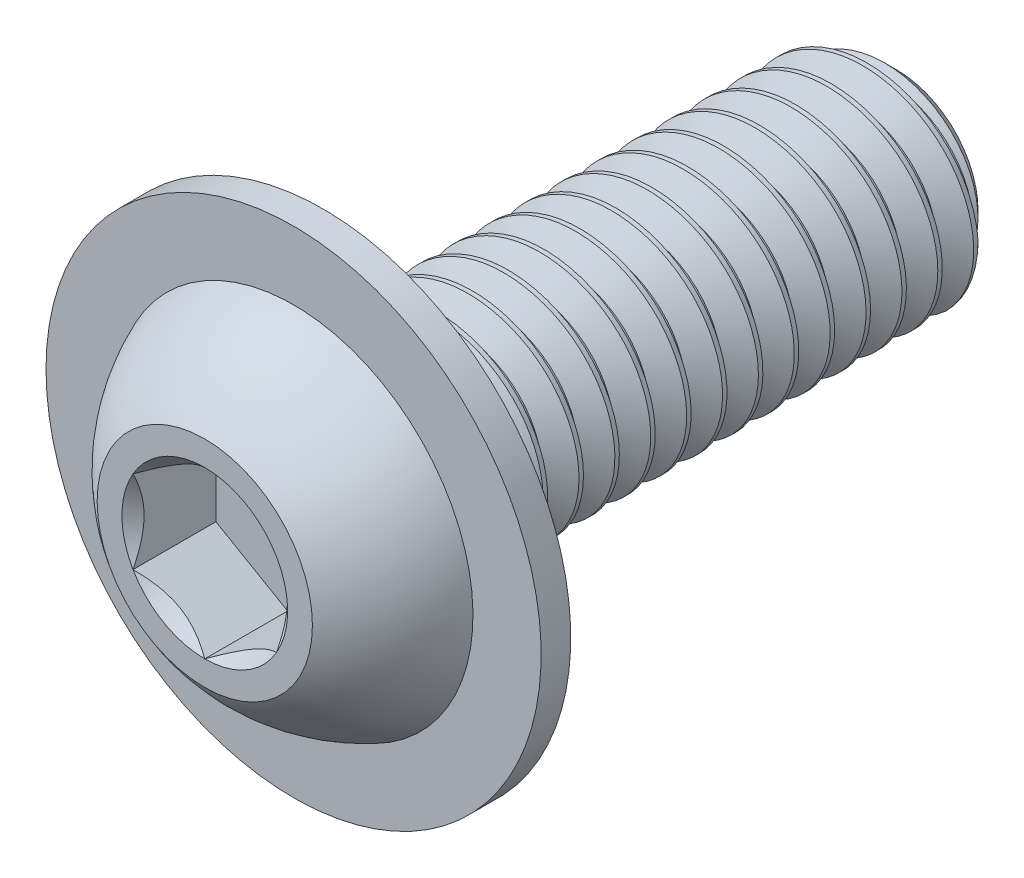
SolidWorks part; units mm, degrees
ref_plane "Front" through (0, 0, 0) normal (0, 0, 1) x (1, 0, 0)
ref_plane "Top" through (0, 0, 0) normal (0, 1, 0) x (1, 0, 0)
ref_plane "Right" through (0, 0, 0) normal (1, 0, 0) x (0, 0, -1)
sketch "Sketch1" plane through (0, 0, 0) normal (1, 0, 0) x (0, 0, -1)
  line L2 (1.65, 1.5) -> (9.65, 1.5)
  line L3 (9.65, 1.5) -> (9.65, 0)
  line L4 (9.65, 0) -> (1.65, 0)
  line L6 (1.2375, 2.5) -> (1.65, 2.5) construction
  line L7 (9.65, 1.5) -> (9.65, -1.5) construction
  line L8 (0, 0) -> (1.65, 0) construction
  line L9 (1.65, 2.5) -> (1.65, -2.5) construction
  line L11 (1.65, 1.5) -> (1.65, 0)
  line L13 (0, 1) -> (0, -1) construction
  line L14 (0, 1) -> (0, 1.5) construction
  line L15 (1.2375, 2.5) -> (1.2375, 3.45) construction
  line L16 (1.2375, 3.45) -> (1.65, 3.45) construction
  line L17 (1.65, 3.45) -> (1.65, 2.5) construction
  line L18 (1.65, 3.45) -> (1.65, -3.45) construction
  arc A3 (0, 1.5) -> (1.2375, 2.5) centre (2.2349, 0) cw construction
  dimension "D1" = 0.4125
revolve "Revolve1" add sketch "Sketch1" angle 360 mid plane about L4
sketch "Sketch3" plane through (0, 0, -9.65) normal (0, 0, -1) x (-1, 0, 0)
  circle A0 centre (0, 0) radius 1.5
curve "Helix/Spiral1" pitch 0.5 height 8.5 radius 1.5 centre (0, 0, -9.65) axis (0, 0, 1) start towards (0, 1, 0)
sketch "Sketch2" plane through (0, 0, 0) normal (1, 0, 0) x (0, 0, -1)
  line L0 (9.65, 1.5) -> (10.0875, 1.5)
  line L1 (10.0875, 1.5) -> (9.9, 1.1752)
  line L2 (9.9, 1.1752) -> (9.8375, 1.1752)
  line L3 (9.8375, 1.1752) -> (9.65, 1.5)
  line L4 (9.7438, 1.3376) -> (9.9938, 1.3376) construction
  dimension "D1" = 60
  dimension "D2" = 0.0625
  dimension "D3" = 0.25
chamfer "Chamfer1" distance 0.375 angle 45 1 edges at (0, 1.5, -9.65)
sweep "Cut-Sweep1" cut profiles "Sketch2" path "Helix/Spiral1" align with end faces yes
sketch "Sketch7" plane through (0, 0, 0) normal (1, 0, 0) x (0, 0, -1)
  line L6 (1.2375, 2.5) -> (1.65, 2.5) construction
  line L8 (0, 0) -> (1.65, 0) construction
  line L11 (1.65, 2.5) -> (1.65, -2.5) construction
  line L12 (1.2375, 2.5) -> (1.65, 2.5)
  line L13 (0, 0) -> (1.65, 0)
  line L14 (0, 1) -> (0, -1) construction
  line L15 (1.65, 2.5) -> (1.65, 0)
  line L16 (0, 1.5) -> (0, 0)
  arc A2 (1.2375, 2.5) -> (0, 1.5) centre (2.2349, 0) ccw construction
  arc A3 (1.2375, 2.5) -> (0, 1.5) centre (2.2349, 0) ccw
revolve "Revolve2" add sketch "Sketch7" angle 360 mid plane about L13
sketch "Sketch11" plane through (0, 0, -1.65) normal (0, 0, -1) x (-1, 0, 0)
  circle A0 centre (0, 0) radius 3.45
extrude "Boss-Extrude3" add sketch "Sketch11" against normal up to vertex (0.4125 mm away) up to point (0, 2.5, -1.2375)
sketch "Sketch5" plane through (0, 0, 0) normal (0, 0, 1) x (1, 0, 0)
  line L1 (1, -0.5774) -> (1, 0.5774)
  line L2 (1, 0.5774) -> (0, 1.1547)
  line L3 (0, 1.1547) -> (-1, 0.5774)
  line L4 (-1, 0.5774) -> (-1, -0.5774)
  line L5 (-1, -0.5774) -> (0, -1.1547)
  line L6 (0, -1.1547) -> (1, -0.5774)
  circle A0 centre (0, 0) radius 1 construction
extrude "Cut-Extrude2" cut sketch "Sketch5" against normal blind 1.155
sketch "Sketch6" plane through (0, 0, 0) normal (0, 0, 1) x (1, 0, 0)
  circle A0 centre (0, 0) radius 1.1547
extrude "Cut-Extrude3" cut sketch "Sketch6" against normal blind 1.155 draft 45
sketch "Sketch9" [suppressed] plane through (0, 0, -5.0546) normal (0, 0, 1) x (1, 0, 0)
  circle A2 centre (0, 0) radius 4.7625
extrude "Boss-Extrude2" [suppressed] add sketch "Sketch9" against normal offset from surface (6.35 mm away) 31.75 up to face at (0, 1.125, -9.65)
sketch "Sketch10" plane through (0, 0, 0) normal (1, 0, 0) x (0, 0, -1)
  line L0 (9.65, 1.5) -> (9.65, -1.5) construction
  point P0 (8.9, -1.5)
  dimension "D1" = 0.75
equation "\"D3@Helix/Spiral1\" = \"Lg@Sketch1\" + \"D4@Helix/Spiral1\""
equation "\"D2@Sketch2\" = \"D4@Helix/Spiral1\" * .125"
equation "\"D3@Sketch2\" = \"D4@Helix/Spiral1\" * .5"
equation "\"D1@Chamfer1\" = \"D4@Helix/Spiral1\" * .75"
equation "\"D1@Cut-Extrude2\" = \"Head Ht@Sketch1\" * .7"
equation "\"D1@Sketch1\" = \"Head Ht@Sketch1\" * .25"
equation "\"D1@Sketch10\" = \"D4@Helix/Spiral1\" * 1.5"
equation "\"D1@Cut-Extrude3\" = \"D1@Cut-Extrude2\""
